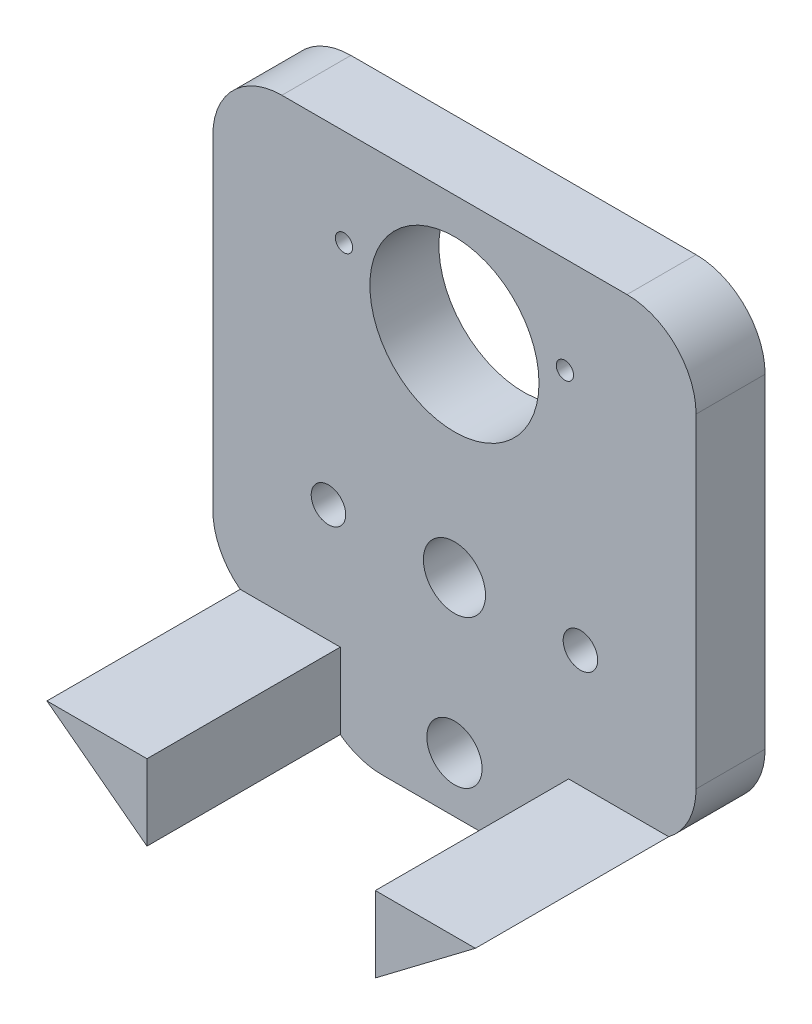
SolidWorks part; units mm, degrees
ref_plane "Front Plane" through (0, 0, 0) normal (0, 0, 1) x (1, 0, 0)
ref_plane "Top Plane" through (0, 0, 0) normal (0, 1, 0) x (1, 0, 0)
ref_plane "Right Plane" through (0, 0, 0) normal (1, 0, 0) x (0, 0, -1)
sketch "Sketch1" plane through (0, 0, 0) normal (0, 0, 1) x (1, 0, 0)
  line L0 (0, 39) -> (0, -39) construction
  line L1 (-35, 39) -> (35, 39)
  line L2 (35, 39) -> (35, -23)
  line L5 (13.8611, -39) -> (-13.8611, -39)
  line L8 (-35, 39) -> (-35, -23)
  line L9 (-35, -23) -> (-13.8611, -39)
  line L10 (13.8611, -39) -> (35, -23)
  dimension "D1" = 70
  dimension "D2" = 27.7222
  dimension "D3" = 78
  dimension "D4" = 62
extrude "Boss-Extrude1" add sketch "Sketch1" along normal blind 10
sketch "Sketch2" plane through (0, 0, 10) normal (0, 0, 1) x (1, 0, 0)
  line L0 (0, 39) -> (0, -39) construction
  line L1 (35, 39) -> (-35, 39) construction
  line L2 (-13.8611, -39) -> (13.8611, -39) construction
  line L3 (-35, 39) -> (-35, -23) construction
  line L6 (-35, 0) -> (35, 0) construction
  line L7 (-35, 39) -> (-35, -23) construction
  line L8 (35, -23) -> (35, 39) construction
  line L9 (-35, 32.3714) -> (35, 32.3714) construction
  line L10 (-24.4305, -31) -> (24.4305, -31) construction
  line L11 (-35, -23) -> (-13.8611, -39) construction
  line L12 (-35, -9) -> (35, -9) construction
  line L13 (13.8611, -39) -> (35, -23) construction
  circle A0 centre (0, -31) radius 4
  circle A1 centre (0, -9) radius 4.5
  circle A2 centre (-18.25, -9) radius 2.5
  circle A3 centre (18.25, -9) radius 2.5
  point P29 (-18.25, -9)
  point P30 (18.25, -9)
  dimension "D1" = 9
  dimension "D2" = 8
  dimension "D3" = 22
  dimension "D4" = 48
  dimension "D7" = 5
  dimension "D8" = 6.6286
  dimension "D9" = 16.75
  dimension "D10" = 35
  dimension "D5" = 18.25
  dimension "D6" = 18.25
extrude "Cut-Extrude1" cut sketch "Sketch2" against normal through all
sketch "Sketch8" plane through (0, 0, 10) normal (0, 0, 1) x (1, 0, 0)
  line L0 (0, 39) -> (0, -4.5) construction
  line L1 (35, 39) -> (-35, 39) construction
  circle A0 centre (0, -9) radius 4.5 construction
  circle A1 centre (0, 21.5139) radius 12.25
  point P15 (0, 0)
  dimension "D1" = 24.5
  dimension "D2" = 17.4861
extrude "Cut-Extrude9" cut sketch "Sketch8" against normal blind 10 contours A1
fillet "Fillet1" radius 10 6 edges at (35, 39, 5) (-35, 39, 5) (35, -23, 5) (13.8611, -39, 5) (-13.8611, -39, 5) (-35, -23, 5)
sketch "Sketch10" plane through (0, 0, 10) normal (0, 0, 1) x (1, 0, 0)
  line L0 (-31.0351, -26.001) -> (-16.5384, -36.9735)
  line L1 (-16.5384, -36.9735) -> (-16.5384, -26.001)
  line L2 (-16.5384, -26.001) -> (-31.0351, -26.001)
extrude "Boss-Extrude2" add sketch "Sketch10" along normal blind 28
ref_plane "Plane1" through (0, 0, 0) normal (1, 0, 0) x (0, 0, -1)
mirror "Mirror1" about plane through (0, 0, 0) normal (1, 0, 0) of "Boss-Extrude2"
sketch "Sketch11" plane through (0, 0, 10) normal (0, 0, 1) x (1, 0, 0)
  line L0 (-35, 29) -> (-35, -18.0275) construction
  line L1 (25, 39) -> (-25, 39) construction
  line L2 (0, 39) -> (0, 13.9159) construction
  line L3 (0, -5.5) -> (0, 5.5) construction
  circle A0 centre (-16, 25) radius 1.25
  circle A1 centre (16, 25) radius 1.25
  dimension "D1" = 2.5
  dimension "D2" = 19
  dimension "D3" = 14
extrude "Cut-Extrude10" cut sketch "Sketch11" against normal blind 10
